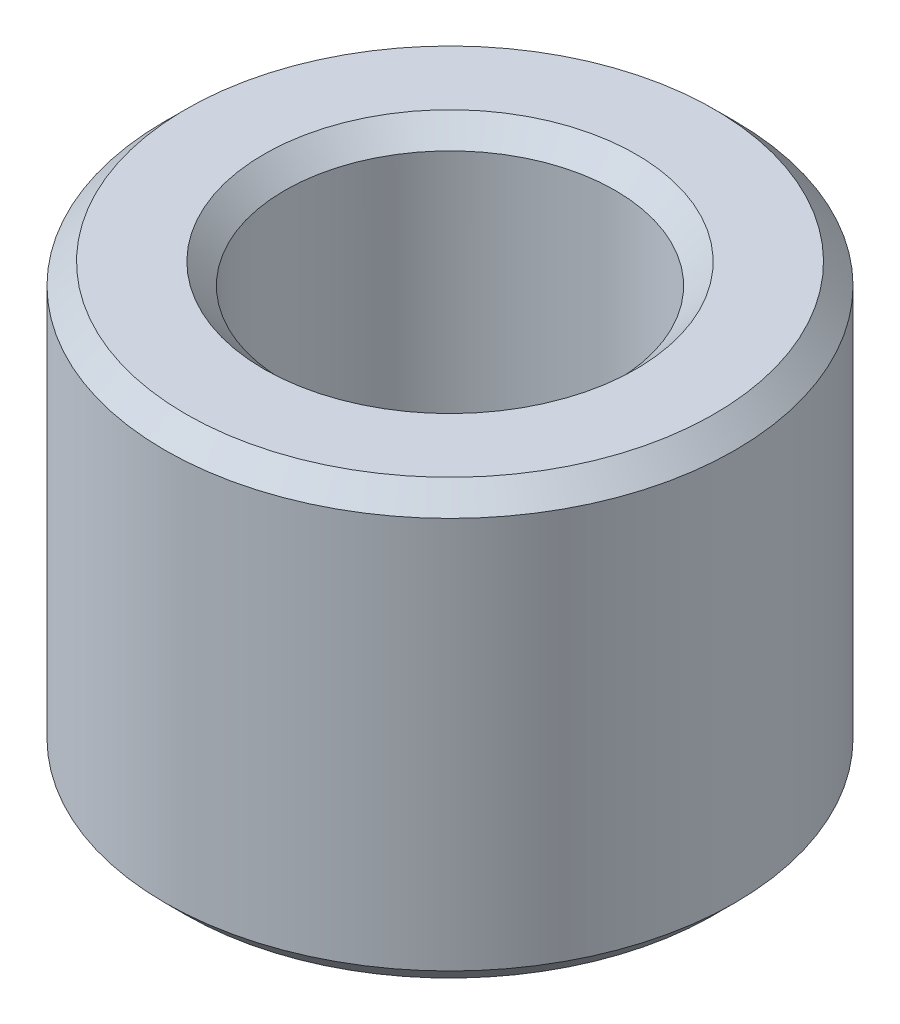
SolidWorks part; units mm, degrees
ref_plane "Front Plane" through (0, 0, 0) normal (0, 0, 1) x (1, 0, 0)
ref_plane "Top Plane" through (0, 0, 0) normal (0, 1, 0) x (1, 0, 0)
ref_plane "Right Plane" through (0, 0, 0) normal (1, 0, 0) x (0, 0, -1)
sketch "Sketch1" plane through (0, 0, 0) normal (0, 1, 0) x (1, 0, 0)
  circle A0 centre (0, 0) radius 50
  dimension "SLEEVE_OD" = 100
extrude "Boss-Extrude1" add sketch "Sketch1" along normal blind 76.0881
sketch "Sketch2" plane through (0, 0, 0) normal (0, 1, 0) x (1, 0, 0)
  circle A0 centre (0, 0) radius 28.9868
  dimension "BORE_D" = 57.9736
extrude "Cut-Extrude1" cut sketch "Sketch2" along normal through all
chamfer "Chamfer1" distance 3.6612 angle 45 4 edges at (0, 76.0881, 28.9868) (0, 0, 28.9868) (0, 0, 50) (0, 76.0881, 50)
